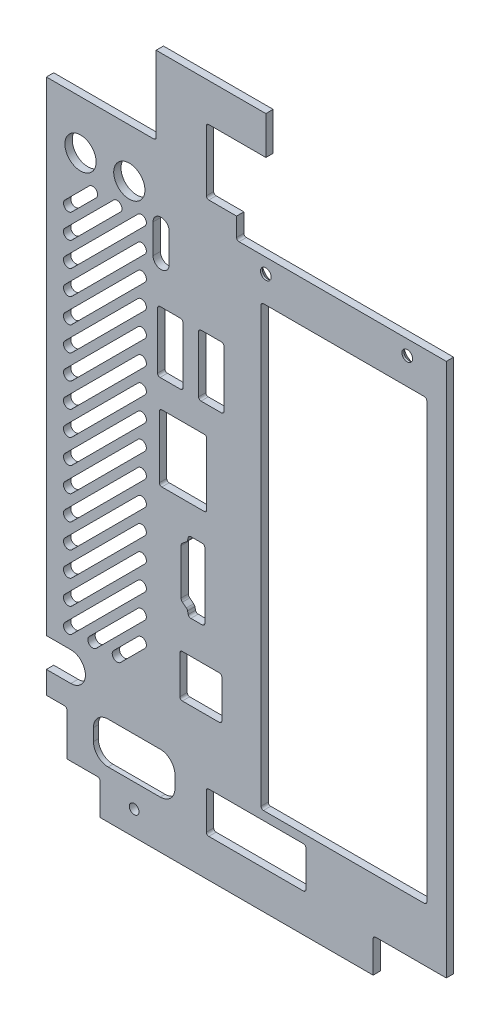
SolidWorks part; units mm, degrees
note: '?' marks a value the reader was unsure of.
ref_plane "前视基准面" through (0, 0, 0) normal (0, 0, 1) x (1, 0, 0)
ref_plane "上视基准面" through (0, 0, 0) normal (0, 1, 0) x (1, 0, 0)
ref_plane "右视基准面" through (0, 0, 0) normal (1, 0, 0) x (0, 0, -1)
sketch "草图1" plane through (0, 0, 0) normal (0, 0, 1) x (1, 0, 0)
  line L2 (-176.1248, 279.7224) -> (-90.1248, 279.7224)
  line L119 (-90.1248, 279.7224) -> (-90.1248, 127.7224)
  line L122 (-90.1248, 127.7224) -> (-176.1248, 127.7224)
  line L125 (-176.1248, 127.7224) -> (-176.1248, 279.7224)
  dimension "D1" = 152
  dimension "D8" = 86
extrude "凸台-拉伸1" add sketch "草图1" along normal blind 1.5
sketch "草图36" plane through (0, 0, 1.5) normal (0, 0, 1) x (1, 0, 0)
  line L0 (-176.1248, 127.7224) -> (-176.1248, 279.7224) construction
  line L1 (-172.1248, 274.7224) -> (-90.1248, 274.7224)
  line L2 (-172.1248, 274.7224) -> (-172.1248, 132.7224)
  line L3 (-172.1248, 132.7224) -> (-90.1248, 132.7224)
  line L4 (-90.1248, 274.7224) -> (-90.1248, 132.7224)
  line L5 (-90.1248, 279.7224) -> (-90.1248, 127.7224) construction
  line L6 (-176.1248, 279.7224) -> (-90.1248, 279.7224) construction
  line L7 (-90.1248, 127.7224) -> (-176.1248, 127.7224) construction
  dimension "D1" = 4
  dimension "D2" = 0
  dimension "D3" = 5
  dimension "D4" = 5
extrude "IO挖空" cut sketch "草图36" against normal blind 10 flip side to cut
sketch "草图38" plane through (0, 0, 0) normal (0, 0, -1) x (-1, 0, 0)
  line L0 (172.1248, 274.7224) -> (172.1248, 132.7224) construction
  line L24 (167.9248, 148.9224) -> (167.9248, 139.7224)
  line L25 (119.1248, 148.7224) -> (139.1248, 148.7224)
  line L26 (119.1248, 148.7224) -> (119.1248, 140.7224)
  line L27 (119.1248, 140.7224) -> (139.1248, 140.7224)
  line L28 (139.1248, 148.7224) -> (139.1248, 140.7224)
  line L35 (172.1248, 132.7224) -> (90.1248, 132.7224) construction
  line L51 (172.1248, 132.7224) -> (161.1248, 132.7224)
  line L52 (172.1248, 274.7224) -> (149.6248, 274.7224)
  line L53 (172.1248, 274.7224) -> (172.1248, 258.7224)
  line L54 (172.1248, 258.7224) -> (149.6248, 258.7224)
  line L55 (149.6248, 274.7224) -> (149.6248, 258.7224)
  line L61 (172.1248, 148.9224) -> (167.9248, 148.9224)
  line L62 (161.1248, 132.7224) -> (161.1248, 139.7224)
  line L69 (172.1248, 132.7224) -> (172.1248, 148.9224)
  line L72 (167.9248, 139.7224) -> (161.1248, 139.7224)
  line L85 (101.1248, 274.7224) -> (90.1248, 274.7224)
  line L86 (90.1248, 274.7224) -> (172.1248, 274.7224) construction
  line L88 (90.1248, 274.7224) -> (90.1248, 257.7224)
  line L89 (90.1248, 274.7224) -> (90.1248, 132.7224) construction
  line L90 (90.1248, 257.7224) -> (101.1248, 257.7224)
  line L94 (101.1248, 257.7224) -> (101.1248, 274.7224)
  line L96 (90.1248, 132.7224) -> (105.1248, 132.7224)
  line L97 (90.1248, 132.7224) -> (90.1248, 139.7224)
  line L98 (90.1248, 139.7224) -> (105.1248, 139.7224)
  line L99 (105.1248, 132.7224) -> (105.1248, 139.7224)
  line L103 (139.3248, 266.9224) -> (115.9248, 266.9224)
  line L104 (139.3248, 266.9224) -> (139.3248, 253.5224)
  line L105 (139.3248, 253.5224) -> (115.9248, 253.5224)
  line L106 (115.9248, 266.9224) -> (115.9248, 253.5224)
  dimension "D2" = 21.2
  dimension "D3" = 8
  dimension "D4" = 20
  dimension "D5" = 16.2
  dimension "D6" = 4.2
  dimension "D7" = 7.8
  dimension "D8" = 32.8
  dimension "D9" = 9.2
  dimension "D10" = 11
  dimension "D11" = 33
extrude "四角挖空" cut sketch "草图38" against normal blind 10
sketch "草图7" plane through (0, 0, 1.5) normal (0, 0, 1) x (1, 0, 0)
  line L0 (-144.7499, 170.6444) -> (-136.1499, 170.6444)
  line L1 (-144.7499, 170.6444) -> (-144.7499, 161.851)
  line L2 (-144.7499, 161.851) -> (-136.1499, 161.851)
  line L3 (-136.1499, 170.6444) -> (-136.1499, 161.851)
  line L4 (-148.9499, 211.4577) -> (-139.2499, 211.4577)
  line L5 (-148.9499, 211.4577) -> (-148.9499, 197.7577)
  line L6 (-148.9499, 197.7577) -> (-139.2499, 197.7577)
  line L7 (-139.2499, 211.4577) -> (-139.2499, 197.7577)
  line L8 (-144.1248, 229.6224) -> (-149.3248, 229.6224)
  line L9 (-144.1248, 229.6224) -> (-144.1248, 217.0224)
  line L10 (-144.1248, 217.0224) -> (-149.3248, 217.0224)
  line L11 (-149.3248, 229.6224) -> (-149.3248, 217.0224)
  line L13 (-140.9248, 229.6224) -> (-135.7248, 229.6224)
  line L14 (-140.9248, 229.6224) -> (-140.9248, 217.0224)
  line L15 (-140.9248, 217.0224) -> (-135.7248, 217.0224)
  line L16 (-135.7248, 229.6224) -> (-135.7248, 217.0224)
  line L18 (-143.4331, 190.516) -> (-144.2193, 189.888)
  line L19 (-143.0354, 191.4831) -> (-143.1729, 190.9231)
  line L20 (-139.6361, 177.952) -> (-139.6361, 191.352)
  line L21 (-143.1729, 178.3808) -> (-143.0354, 177.8208)
  line L22 (-144.2193, 179.416) -> (-143.4331, 178.788)
  line L23 (-142.5012, 191.902) -> (-140.1861, 191.902)
  line L24 (-144.5012, 189.302) -> (-144.5012, 180.002)
  line L25 (-142.5012, 177.402) -> (-140.1861, 177.402)
  line L42 (-90.1248, 257.7224) -> (-90.1248, 139.7224) construction
  line L43 (-172.1248, 258.7224) -> (-149.6248, 258.7224) construction
  line L44 (-172.1248, 258.7224) -> (-172.1248, 148.9224) construction
  line L45 (-150.2548, 243.9224) -> (-146.9548, 243.9224) construction
  line L46 (-150.2548, 243.9224) -> (-150.2548, 237.9224)
  line L47 (-150.2548, 237.9224) -> (-146.9548, 237.9224) construction
  line L48 (-146.9548, 243.9224) -> (-146.9548, 237.9224)
  arc A2 (-144.2193, 189.888) -> (-144.5012, 189.302) centre (-143.7512, 189.302) ccw
  arc A3 (-143.4331, 190.516) -> (-143.1729, 190.9231) centre (-143.9012, 191.102) ccw
  arc A4 (-142.5012, 191.902) -> (-143.0354, 191.4831) centre (-142.5012, 191.352) ccw
  arc A5 (-139.6361, 191.352) -> (-140.1861, 191.902) centre (-140.1861, 191.352) ccw
  arc A6 (-140.1861, 177.402) -> (-139.6361, 177.952) centre (-140.1861, 177.952) ccw
  arc A7 (-143.0354, 177.8208) -> (-142.5012, 177.402) centre (-142.5012, 177.952) ccw
  arc A8 (-143.1729, 178.3808) -> (-143.4331, 178.788) centre (-143.9012, 178.202) ccw
  arc A9 (-144.5012, 180.002) -> (-144.2193, 179.416) centre (-143.7512, 180.002) ccw
  arc A18 (-146.9548, 243.9224) -> (-150.2548, 243.9224) centre (-148.6048, 243.9224) ccw
  arc A19 (-146.9548, 237.9224) -> (-150.2548, 237.9224) centre (-148.6048, 237.9224) cw
  dimension "D6" = 6
  dimension "D14" = 29.1
  dimension "D16" = 29.1
  dimension "D13" = 5.2
  dimension "D2" = 6.7576
  dimension "D3" = 5.8557
  dimension "D4" = 45.6
  dimension "D5" = 5.2
  dimension "D7" = 14.5
  dimension "D8" = 8.7934
  dimension "D9" = 13.7
  dimension "D10" = 12.6
  dimension "D11" = 12.6
  dimension "D12" = 3.3
  dimension "D15" = 3.2
  dimension "D17" = 23.175
extrude "NUC-IO" cut sketch "草图7" against normal blind 2
sketch "草图25" plane through (0, 0, 1.5) normal (0, 0, 1) x (1, 0, 0)
  line L3 (-133.1248, 256.7224) -> (-92.1248, 256.7224)
  line L10 (-128.1248, 150.7224) -> (-94.1248, 150.7224)
  line L27 (-92.1248, 256.7224) -> (-92.1248, 249.2224)
  line L31 (-128.1248, 240.7224) -> (-128.1248, 150.7224)
  line L32 (-161.1248, 132.7224) -> (-105.1248, 132.7224) construction
  line L39 (-92.1248, 249.2224) -> (-133.1248, 249.2224)
  line L40 (-133.1248, 256.7224) -> (-133.1248, 249.2224)
  line L43 (-128.1248, 240.7224) -> (-94.1248, 240.7224)
  line L45 (-94.1248, 240.7224) -> (-94.1248, 150.7224)
  line L47 (-101.1248, 274.7224) -> (-149.6248, 274.7224) construction
  line L48 (-90.1248, 257.7224) -> (-90.1248, 139.7224) construction
  line L49 (-90.1248, 257.7224) -> (-90.1248, 139.7224) construction
  circle A0 centre (-98.1248, 246.2224) radius 1
  circle A1 centre (-127.1248, 246.2224) radius 1
  point P13 (-92.1248, 256.7224)
  dimension "D6" = 41
  dimension "D7" = 5.5
  dimension "D8" = 6
  dimension "D3" = 18
  dimension "D9" = 6
  dimension "D2" = 2
  dimension "D4" = 90
  dimension "D5" = 8.5
  dimension "D10" = 5.5
  dimension "D11" = 18
  dimension "D12" = 4
extrude "PCI-E" cut sketch "草图25" against normal blind 10
sketch "草图31" plane through (0, 0, 1.5) normal (0, 0, 1) x (1, 0, 0)
  line L0 (-172.1248, 258.7224) -> (-172.1248, 148.9224) construction
  line L6 (-162.4748, 148.0224) -> (-162.4748, 145.5224)
  line L19 (-159.4748, 148.0224) -> (-148.7748, 148.0224) construction
  line L20 (-159.4748, 148.0224) -> (-159.4748, 145.5224) construction
  line L21 (-159.4748, 145.5224) -> (-148.7748, 145.5224) construction
  line L22 (-148.7748, 148.0224) -> (-148.7748, 145.5224) construction
  line L23 (-159.4748, 151.0224) -> (-148.7748, 151.0224)
  line L24 (-154.1248, 151.0224) -> (-154.1248, 137.7224) construction
  line L25 (-145.7748, 148.0224) -> (-145.7748, 145.5224)
  line L26 (-159.4748, 142.5224) -> (-148.7748, 142.5224)
  circle A0 centre (-154.1248, 137.7224) radius 1
  arc A5 (-159.4748, 151.0224) -> (-162.4748, 148.0224) centre (-159.4748, 148.0224) ccw
  arc A6 (-162.4748, 145.5224) -> (-159.4748, 142.5224) centre (-159.4748, 145.5224) ccw
  arc A11 (-145.7748, 148.0224) -> (-148.7748, 151.0224) centre (-148.7748, 148.0224) ccw
  arc A12 (-148.7748, 142.5224) -> (-145.7748, 145.5224) centre (-148.7748, 145.5224) ccw
  dimension "D5" = 8.5
  dimension "D1" = 2.5
  dimension "D2" = 10.7
  dimension "D3" = 4.8
  dimension "D4" = 18
extrude "Power" cut sketch "草图31" against normal blind 10
hole_wizard "打孔尺寸(%根据)内六角花形半沉头螺钉的类型1" [suppressed] positions "草图34" profile "草图35" countersink size "M6" standard "GB"
sketch "草图34" plane through (0, 0, 1.5) normal (0, 0, 1) x (1, 0, 0)
  point P0 (-154.1248, 137.7224)
sketch "草图35" plane through (-154.1248, 137.7224, 1.5) normal (1, 0, 0) x (0, -1, 0)
  line L0 (0, 0) -> (0, 1.5)
  line L1 (0, 1.5) -> (1.1, 1.5)
  line L2 (1.1, 1.5) -> (1.1, 1)
  line L3 (1.1, 1) -> (2.1, 0)
  line L5 (2.1, 0) -> (0, 0)
  line L6 (-1.1, 1) -> (-2.1, 0) construction
  line L11 (0, -6.35) -> (0, 107.95) construction
  dimension "通孔孔直径" = 2.2
  dimension "通孔孔深度" = 1.5
  dimension "近端锥形沉头孔直径" = 4.2
  dimension "近端锥形沉头孔角度" = 90
sketch "草图39" plane through (0, 0, 0) normal (0, 0, -1) x (-1, 0, 0)
  line L0 (101.1248, 274.7224) -> (149.6248, 274.7224) construction
  line L1 (114.1248, 271.7224) -> (151.1248, 271.7224) construction
  line L2 (114.1248, 271.7224) -> (114.1248, 135.7224) construction
  line L3 (114.1248, 135.7224) -> (151.1248, 135.7224) construction
  line L4 (151.1248, 271.7224) -> (151.1248, 135.7224) construction
  line L5 (161.1248, 132.7224) -> (105.1248, 132.7224) construction
  line L6 (90.1248, 257.7224) -> (90.1248, 139.7224) construction
  line L7 (172.1248, 258.7224) -> (172.1248, 148.9224) construction
  circle A0 centre (114.1248, 271.7224) radius 1
  circle A1 centre (151.1248, 271.7224) radius 1
  circle A2 centre (114.1248, 135.7224) radius 1
  circle A3 centre (151.1248, 135.7224) radius 1
  dimension "D1" = 3
  dimension "D2" = 3
  dimension "D3" = 24
  dimension "D4" = 21
extrude "IO孔位" [suppressed] cut sketch "草图39" against normal blind 10
sketch "草图46" plane through (0, 0, 1.5) normal (0, 0, 1) x (1, 0, 0)
  line L0 (-177.3005, 156.5224) -> (-167.1248, 156.5224) construction
  line L1 (-177.3005, 159.5224) -> (-167.1248, 159.5224)
  line L2 (-177.3005, 153.5224) -> (-167.1248, 153.5224)
  line L3 (-148.7748, 151.0224) -> (-159.4748, 151.0224) construction
  line L6 (-172.1248, 258.7224) -> (-172.1248, 148.9224) construction
  arc A1 (-177.3005, 159.5224) -> (-177.3005, 153.5224) centre (-177.3005, 156.5224) ccw
  arc A2 (-167.1248, 153.5224) -> (-167.1248, 159.5224) centre (-167.1248, 156.5224) ccw
  circle A3 centre (-167.1248, 156.5224) radius 2.5 construction
  point P2 (-172.2127, 156.5224)
  dimension "D1" = 5
  dimension "D2" = 5.5
extrude "电线口" cut sketch "草图46" against normal blind 2
sketch "草图48" plane through (0, 0, 0) normal (0, 0, -1) x (-1, 0, 0)
  line L5 (133.1248, 259.8891) -> (127.1248, 259.8891)
  line L10 (127.1248, 259.8891) -> (127.1248, 275.7397)
  line L11 (133.1248, 249.2224) -> (90.1248, 249.2224)
  line L12 (133.1248, 249.2224) -> (133.1248, 259.8891)
  line L13 (127.1248, 275.7397) -> (90.1248, 275.7397)
  line L14 (90.1248, 249.2224) -> (90.1248, 275.7397)
  line L15 (172.1248, 258.7224) -> (172.1248, 159.5224) construction
  dimension "D1" = 45
extrude "切除-拉伸1" cut sketch "草图48" against normal blind 10
sketch "草图49" plane through (0, 0, 0) normal (0, 0, -1) x (-1, 0, 0)
  line L0 (94.1248, 240.7224) -> (128.1248, 240.7224) construction
  line L1 (110.3748, 240.7224) -> (114.3748, 240.7224)
  line L2 (110.3748, 240.7224) -> (110.3748, 150.7224)
  line L3 (110.3748, 150.7224) -> (114.3748, 150.7224)
  line L4 (114.3748, 240.7224) -> (114.3748, 150.7224)
  line L5 (128.1248, 150.7224) -> (94.1248, 150.7224) construction
  line L6 (94.1248, 150.7224) -> (94.1248, 240.7224) construction
  dimension "D1" = 4
  dimension "D2" = 16.25
extrude "凸台-拉伸2" [suppressed] add sketch "草图49" against normal blind 1.5
fillet "R1" [suppressed] radius 1
sketch "草图50" plane through (0, 0, 1.5) normal (0, 0, 1) x (1, 0, 0)
  point P0 (-167.1248, 156.5224)
other "线路点1"
ref_plane "基准面1" through (-167.1248, 0, 0) normal (-1, 0, 0) x (0, 0, 1)
sketch3d "3D草图2"
  line L1 (-167.1248, 156.5224, 1.5) -> (-167.1248, 156.5224, 4.5875) construction
  line L3 (-167.1248, 156.5224, 1.8291) -> (-167.1248, 156.5224, -0.8657)
ref_axis "基准轴1" through (-167.1248, 156.5224, 1.8291) along (0, 0, -1)?
sketch "草图54" plane through (0, 0, 1.5) normal (0, 0, 1) x (1, 0, 0)
  line L0 (-127.1248, 274.7224) -> (-149.6248, 274.7224) construction
  line L1 (-172.1248, 258.7224) -> (-172.1248, 159.5224) construction
  circle A0 centre (-155.1248, 248.7224) radius 3.2
  circle A1 centre (-165.1248, 248.7224) radius 3.2
  circle A2 centre (-165.1248, 248.7224) radius 4.5 construction
  circle A3 centre (-155.1248, 248.7224) radius 4.5 construction
  dimension "D1" = 26
  dimension "D2" = 10
  dimension "D3" = 7
extrude "SMA" cut sketch "草图54" against normal blind 1.5
hole_wizard "打孔尺寸(%根据)内六角花形沉头螺钉的类型1" positions "草图55" profile "草图56" countersink size "M6" standard "GB" end condition through all
sketch "草图55" plane through (0, 0, 0) normal (0, 0, -1) x (-1, 0, 0)
  point P0 (98.1248, 246.2224)
  point P3 (127.1248, 246.2224)
sketch "草图56" plane through (-98.1248, 246.2224, 0) normal (1, 0, 0) x (0, 1, 0)
  line L0 (0, 0) -> (0, 1.5)
  line L1 (0, 1.5) -> (1.1, 1.5)
  line L2 (1.1, 1.5) -> (1.1, 1.1)
  line L3 (1.1, 1.1) -> (2.2, 0)
  line L5 (2.2, 0) -> (0, 0)
  line L6 (-1.1, 1.1) -> (-2.2, 0) construction
  line L11 (0, -6.35) -> (0, 107.95) construction
  dimension "通孔孔直径" = 2.2
  dimension "通孔孔深度" = 1.5
  dimension "近端锥形沉头孔直径" = 4.4
  dimension "近端锥形沉头孔角度" = 90
sketch "草图57" plane through (0, 0, 0) normal (0, 0, -1) x (-1, 0, 0)
  line L0 (119.1248, 148.7224) -> (119.1248, 140.7224) construction
  line L1 (118.9248, 148.9224) -> (139.3248, 148.9224)
  line L2 (118.9248, 148.9224) -> (118.9248, 140.5224)
  line L3 (118.9248, 140.5224) -> (139.3248, 140.5224)
  line L4 (139.3248, 148.9224) -> (139.3248, 140.5224)
  line L5 (139.1248, 140.7224) -> (139.1248, 148.7224) construction
  line L6 (119.1248, 140.7224) -> (139.1248, 140.7224) construction
  line L7 (139.1248, 148.7224) -> (119.1248, 148.7224) construction
  dimension "D1" = 0.2
  dimension "D2" = 0.2
  dimension "D3" = 0.2
  dimension "D4" = 0.2
extrude "切除-拉伸4" cut sketch "草图57" against normal blind 10
fillet "圆角1" radius 0.5 7 edges at (-139.3248, 253.5224, 0.75) (-139.3248, 266.9224, 0.75) (-167.9248, 148.9224, 0.75) (-139.3248, 140.5224, 0.75) (-118.9248, 140.5224, 0.75) (-139.3248, 148.9224, 0.75) (-118.9248, 148.9224, 0.75)
sketch "草图59" plane through (0, 0, 0) normal (0, 0, -1) x (-1, 0, 0)
  line L1 (144.1248, 152.7724) -> (164.1248, 152.7724)
  line L2 (144.1248, 152.7724) -> (144.1248, 140.7724)
  line L3 (144.1248, 140.7724) -> (164.1248, 140.7724)
  line L4 (164.1248, 152.7724) -> (164.1248, 140.7724)
  line L5 (159.4748, 142.5224) -> (148.7748, 142.5224) construction
  line L12 (162.4748, 148.0224) -> (162.4748, 145.5224) construction
  dimension "D1" = 20
  dimension "D2" = 12
  dimension "D3" = 1.75
  dimension "D4" = 1.65
extrude "切除-拉伸5" cut sketch "草图59" against normal blind 0.5
fillet "圆角3" radius 0.5 4 edges at (-144.1248, 140.7724, 0.25) (-164.1248, 140.7724, 0.25) (-164.1248, 152.7724, 0.25) (-144.1248, 152.7724, 0.25)
sketch "草图61" plane through (0, 0, 1.5) normal (0, 0, 1) x (1, 0, 0)
  line L0 (-153.1248, 240.9224) -> (-167.1248, 240.9224) construction
  line L1 (-153.1248, 239.4224) -> (-167.1248, 239.4224)
  line L2 (-153.1248, 242.4224) -> (-167.1248, 242.4224)
  line L3 (-172.1248, 258.7224) -> (-172.1248, 159.5224) construction
  line L5 (-153.1248, 236.3724) -> (-167.1248, 236.3724) construction
  line L6 (-153.1248, 234.8724) -> (-167.1248, 234.8724)
  line L7 (-153.1248, 237.8724) -> (-167.1248, 237.8724)
  line L8 (-153.1248, 231.8224) -> (-167.1248, 231.8224) construction
  line L9 (-153.1248, 230.3224) -> (-167.1248, 230.3224)
  line L10 (-153.1248, 233.3224) -> (-167.1248, 233.3224)
  line L11 (-153.1248, 227.2724) -> (-167.1248, 227.2724) construction
  line L12 (-153.1248, 225.7724) -> (-167.1248, 225.7724)
  line L13 (-153.1248, 228.7724) -> (-167.1248, 228.7724)
  line L14 (-153.1248, 222.7224) -> (-167.1248, 222.7224) construction
  line L15 (-153.1248, 221.2224) -> (-167.1248, 221.2224)
  line L16 (-153.1248, 224.2224) -> (-167.1248, 224.2224)
  line L17 (-153.1248, 218.1724) -> (-167.1248, 218.1724) construction
  line L18 (-153.1248, 216.6724) -> (-167.1248, 216.6724)
  line L19 (-153.1248, 219.6724) -> (-167.1248, 219.6724)
  line L20 (-153.1248, 213.6224) -> (-167.1248, 213.6224) construction
  line L21 (-153.1248, 212.1224) -> (-167.1248, 212.1224)
  line L22 (-153.1248, 215.1224) -> (-167.1248, 215.1224)
  line L23 (-153.1248, 209.0724) -> (-167.1248, 209.0724) construction
  line L24 (-153.1248, 207.5724) -> (-167.1248, 207.5724)
  line L25 (-153.1248, 210.5724) -> (-167.1248, 210.5724)
  line L26 (-153.1248, 204.5224) -> (-167.1248, 204.5224) construction
  line L27 (-153.1248, 203.0224) -> (-167.1248, 203.0224)
  line L28 (-153.1248, 206.0224) -> (-167.1248, 206.0224)
  line L29 (-153.1248, 199.9724) -> (-167.1248, 199.9724) construction
  line L30 (-153.1248, 198.4724) -> (-167.1248, 198.4724)
  line L31 (-153.1248, 201.4724) -> (-167.1248, 201.4724)
  line L32 (-153.1248, 195.4224) -> (-167.1248, 195.4224) construction
  line L33 (-153.1248, 193.9224) -> (-167.1248, 193.9224)
  line L34 (-153.1248, 196.9224) -> (-167.1248, 196.9224)
  line L35 (-153.1248, 190.8724) -> (-167.1248, 190.8724) construction
  line L36 (-153.1248, 189.3724) -> (-167.1248, 189.3724)
  line L37 (-153.1248, 192.3724) -> (-167.1248, 192.3724)
  line L38 (-153.1248, 186.3224) -> (-167.1248, 186.3224) construction
  line L39 (-153.1248, 184.8224) -> (-167.1248, 184.8224)
  line L40 (-153.1248, 187.8224) -> (-167.1248, 187.8224)
  line L41 (-153.1248, 181.7724) -> (-167.1248, 181.7724) construction
  line L42 (-153.1248, 180.2724) -> (-167.1248, 180.2724)
  line L43 (-153.1248, 183.2724) -> (-167.1248, 183.2724)
  line L44 (-153.1248, 177.2224) -> (-167.1248, 177.2224) construction
  line L45 (-153.1248, 175.7224) -> (-167.1248, 175.7224)
  line L46 (-153.1248, 178.7224) -> (-167.1248, 178.7224)
  line L47 (-153.1248, 172.6724) -> (-167.1248, 172.6724) construction
  line L48 (-153.1248, 171.1724) -> (-167.1248, 171.1724)
  line L49 (-153.1248, 174.1724) -> (-167.1248, 174.1724)
  line L50 (-153.1248, 168.1224) -> (-167.1248, 168.1224) construction
  line L51 (-153.1248, 166.6224) -> (-167.1248, 166.6224)
  line L52 (-153.1248, 169.6224) -> (-167.1248, 169.6224)
  line L53 (-153.1248, 163.5724) -> (-167.1248, 163.5724) construction
  line L54 (-153.1248, 162.0724) -> (-167.1248, 162.0724)
  line L55 (-153.1248, 165.0724) -> (-167.1248, 165.0724)
  arc A0 (-153.1248, 239.4224) -> (-153.1248, 242.4224) centre (-153.1248, 240.9224) ccw
  arc A1 (-167.1248, 242.4224) -> (-167.1248, 239.4224) centre (-167.1248, 240.9224) ccw
  arc A2 (-153.1248, 234.8724) -> (-153.1248, 237.8724) centre (-153.1248, 236.3724) ccw
  arc A3 (-167.1248, 237.8724) -> (-167.1248, 234.8724) centre (-167.1248, 236.3724) ccw
  arc A4 (-153.1248, 230.3224) -> (-153.1248, 233.3224) centre (-153.1248, 231.8224) ccw
  arc A5 (-167.1248, 233.3224) -> (-167.1248, 230.3224) centre (-167.1248, 231.8224) ccw
  arc A6 (-153.1248, 225.7724) -> (-153.1248, 228.7724) centre (-153.1248, 227.2724) ccw
  arc A7 (-167.1248, 228.7724) -> (-167.1248, 225.7724) centre (-167.1248, 227.2724) ccw
  arc A8 (-153.1248, 221.2224) -> (-153.1248, 224.2224) centre (-153.1248, 222.7224) ccw
  arc A9 (-167.1248, 224.2224) -> (-167.1248, 221.2224) centre (-167.1248, 222.7224) ccw
  arc A10 (-153.1248, 216.6724) -> (-153.1248, 219.6724) centre (-153.1248, 218.1724) ccw
  arc A11 (-167.1248, 219.6724) -> (-167.1248, 216.6724) centre (-167.1248, 218.1724) ccw
  arc A12 (-153.1248, 212.1224) -> (-153.1248, 215.1224) centre (-153.1248, 213.6224) ccw
  arc A13 (-167.1248, 215.1224) -> (-167.1248, 212.1224) centre (-167.1248, 213.6224) ccw
  arc A14 (-153.1248, 207.5724) -> (-153.1248, 210.5724) centre (-153.1248, 209.0724) ccw
  arc A15 (-167.1248, 210.5724) -> (-167.1248, 207.5724) centre (-167.1248, 209.0724) ccw
  arc A16 (-153.1248, 203.0224) -> (-153.1248, 206.0224) centre (-153.1248, 204.5224) ccw
  arc A17 (-167.1248, 206.0224) -> (-167.1248, 203.0224) centre (-167.1248, 204.5224) ccw
  arc A18 (-153.1248, 198.4724) -> (-153.1248, 201.4724) centre (-153.1248, 199.9724) ccw
  arc A19 (-167.1248, 201.4724) -> (-167.1248, 198.4724) centre (-167.1248, 199.9724) ccw
  arc A20 (-153.1248, 193.9224) -> (-153.1248, 196.9224) centre (-153.1248, 195.4224) ccw
  arc A21 (-167.1248, 196.9224) -> (-167.1248, 193.9224) centre (-167.1248, 195.4224) ccw
  arc A22 (-153.1248, 189.3724) -> (-153.1248, 192.3724) centre (-153.1248, 190.8724) ccw
  arc A23 (-167.1248, 192.3724) -> (-167.1248, 189.3724) centre (-167.1248, 190.8724) ccw
  arc A24 (-153.1248, 184.8224) -> (-153.1248, 187.8224) centre (-153.1248, 186.3224) ccw
  arc A25 (-167.1248, 187.8224) -> (-167.1248, 184.8224) centre (-167.1248, 186.3224) ccw
  arc A26 (-153.1248, 180.2724) -> (-153.1248, 183.2724) centre (-153.1248, 181.7724) ccw
  arc A27 (-167.1248, 183.2724) -> (-167.1248, 180.2724) centre (-167.1248, 181.7724) ccw
  arc A28 (-153.1248, 175.7224) -> (-153.1248, 178.7224) centre (-153.1248, 177.2224) ccw
  arc A29 (-167.1248, 178.7224) -> (-167.1248, 175.7224) centre (-167.1248, 177.2224) ccw
  arc A30 (-153.1248, 171.1724) -> (-153.1248, 174.1724) centre (-153.1248, 172.6724) ccw
  arc A31 (-167.1248, 174.1724) -> (-167.1248, 171.1724) centre (-167.1248, 172.6724) ccw
  arc A32 (-153.1248, 166.6224) -> (-153.1248, 169.6224) centre (-153.1248, 168.1224) ccw
  arc A33 (-167.1248, 169.6224) -> (-167.1248, 166.6224) centre (-167.1248, 168.1224) ccw
  arc A34 (-153.1248, 162.0724) -> (-153.1248, 165.0724) centre (-153.1248, 163.5724) ccw
  arc A35 (-167.1248, 165.0724) -> (-167.1248, 162.0724) centre (-167.1248, 163.5724) ccw
  point P2 (-160.1248, 240.9224)
  point P12 (-160.1248, 236.3724)
  point P19 (-160.1248, 231.8224)
  point P26 (-160.1248, 227.2724)
  point P33 (-160.1248, 222.7224)
  point P40 (-160.1248, 218.1724)
  point P47 (-160.1248, 213.6224)
  point P54 (-160.1248, 209.0724)
  point P61 (-160.1248, 204.5224)
  point P68 (-160.1248, 199.9724)
  point P75 (-160.1248, 195.4224)
  point P82 (-160.1248, 190.8724)
  point P89 (-160.1248, 186.3224)
  point P96 (-160.1248, 181.7724)
  point P103 (-160.1248, 177.2224)
  point P110 (-160.1248, 172.6724)
  point P117 (-160.1248, 168.1224)
  point P124 (-160.1248, 163.5724)
  dimension "D2" = 18
  dimension "D1" = 5
extrude "切除-拉伸6" [suppressed] cut sketch "草图61" against normal blind 10
sketch "草图62" plane through (0, 0, 1.5) normal (0, 0, 1) x (1, 0, 0)
  line L0 (-172.1248, 258.7224) -> (-172.1248, 159.5224) construction
  line L1 (-152.6248, 243.9224) -> (-167.6248, 243.9224) construction
  line L2 (-152.6248, 243.9224) -> (-152.6248, 163.0655) construction
  line L3 (-152.6248, 163.0655) -> (-167.6248, 163.0655) construction
  line L4 (-167.6248, 243.9224) -> (-167.6248, 163.0655) construction
  line L5 (-167.6248, 163.0655) -> (-152.6248, 178.0655) construction
  line L6 (-168.332, 163.7726) -> (-153.332, 178.7726)
  line L7 (-166.9177, 162.3584) -> (-151.9177, 177.3584)
  line L8 (-167.6248, 168.0655) -> (-152.6248, 183.0655) construction
  line L9 (-168.332, 168.7726) -> (-153.332, 183.7726)
  line L10 (-166.9177, 167.3584) -> (-151.9177, 182.3584)
  line L11 (-167.6248, 173.0655) -> (-152.6248, 188.0655) construction
  line L12 (-168.332, 173.7726) -> (-153.332, 188.7726)
  line L13 (-166.9177, 172.3584) -> (-151.9177, 187.3584)
  line L14 (-167.6248, 178.0655) -> (-152.6248, 193.0655) construction
  line L15 (-168.332, 178.7726) -> (-153.332, 193.7726)
  line L16 (-166.9177, 177.3584) -> (-151.9177, 192.3584)
  line L17 (-167.6248, 183.0655) -> (-152.6248, 198.0655) construction
  line L18 (-168.332, 183.7726) -> (-153.332, 198.7726)
  line L19 (-166.9177, 182.3584) -> (-151.9177, 197.3584)
  line L20 (-167.6248, 188.0655) -> (-152.6248, 203.0655) construction
  line L21 (-168.332, 188.7726) -> (-153.332, 203.7726)
  line L22 (-166.9177, 187.3584) -> (-151.9177, 202.3584)
  line L23 (-167.6248, 193.0655) -> (-152.6248, 208.0655) construction
  line L24 (-168.332, 193.7726) -> (-153.332, 208.7726)
  line L25 (-166.9177, 192.3584) -> (-151.9177, 207.3584)
  line L26 (-167.6248, 198.0655) -> (-152.6248, 213.0655) construction
  line L27 (-168.332, 198.7726) -> (-153.332, 213.7726)
  line L28 (-166.9177, 197.3584) -> (-151.9177, 212.3584)
  line L29 (-167.6248, 203.0655) -> (-152.6248, 218.0655) construction
  line L30 (-168.332, 203.7726) -> (-153.332, 218.7726)
  line L31 (-166.9177, 202.3584) -> (-151.9177, 217.3584)
  line L32 (-167.6248, 208.0655) -> (-152.6248, 223.0655) construction
  line L33 (-168.332, 208.7726) -> (-153.332, 223.7726)
  line L34 (-166.9177, 207.3584) -> (-151.9177, 222.3584)
  line L35 (-167.6248, 213.0655) -> (-152.6248, 228.0655) construction
  line L36 (-168.332, 213.7726) -> (-153.332, 228.7726)
  line L37 (-166.9177, 212.3584) -> (-151.9177, 227.3584)
  line L38 (-167.6248, 218.0655) -> (-152.6248, 233.0655) construction
  line L39 (-168.332, 218.7726) -> (-153.332, 233.7726)
  line L40 (-166.9177, 217.3584) -> (-151.9177, 232.3584)
  line L41 (-167.6248, 223.0655) -> (-152.6248, 238.0655) construction
  line L42 (-168.332, 223.7726) -> (-153.332, 238.7726)
  line L43 (-166.9177, 222.3584) -> (-151.9177, 237.3584)
  line L44 (-167.6248, 228.0655) -> (-152.6248, 243.0655) construction
  line L45 (-168.332, 228.7726) -> (-153.332, 243.7726)
  line L46 (-166.9177, 227.3584) -> (-151.9177, 242.3584)
  line L47 (-162.6248, 163.0655) -> (-152.6248, 173.0655) construction
  line L50 (-163.332, 163.7726) -> (-153.332, 173.7726)
  line L51 (-161.9177, 162.3584) -> (-151.9177, 172.3584)
  line L52 (-152.6248, 168.0655) -> (-157.6248, 163.0655) construction
  line L53 (-151.9177, 167.3584) -> (-156.9177, 162.3584)
  line L54 (-153.332, 168.7726) -> (-158.332, 163.7726)
  line L55 (-152.6248, 243.0655) -> (-167.6248, 243.0655) construction
  line L57 (-157.6248, 243.0655) -> (-167.6248, 233.0655) construction
  line L58 (-156.9177, 242.3584) -> (-166.9177, 232.3584)
  line L59 (-158.332, 243.7726) -> (-168.332, 233.7726)
  line L60 (-162.6248, 243.0655) -> (-167.6248, 238.0655) construction
  line L61 (-161.9177, 242.3584) -> (-166.9177, 237.3584)
  line L62 (-163.332, 243.7726) -> (-168.332, 238.7726)
  arc A0 (-168.332, 163.7726) -> (-166.9177, 162.3584) centre (-167.6248, 163.0655) ccw
  arc A1 (-151.9177, 177.3584) -> (-153.332, 178.7726) centre (-152.6248, 178.0655) ccw
  arc A2 (-168.332, 168.7726) -> (-166.9177, 167.3584) centre (-167.6248, 168.0655) ccw
  arc A3 (-151.9177, 182.3584) -> (-153.332, 183.7726) centre (-152.6248, 183.0655) ccw
  arc A4 (-168.332, 173.7726) -> (-166.9177, 172.3584) centre (-167.6248, 173.0655) ccw
  arc A5 (-151.9177, 187.3584) -> (-153.332, 188.7726) centre (-152.6248, 188.0655) ccw
  arc A6 (-168.332, 178.7726) -> (-166.9177, 177.3584) centre (-167.6248, 178.0655) ccw
  arc A7 (-151.9177, 192.3584) -> (-153.332, 193.7726) centre (-152.6248, 193.0655) ccw
  arc A8 (-168.332, 183.7726) -> (-166.9177, 182.3584) centre (-167.6248, 183.0655) ccw
  arc A9 (-151.9177, 197.3584) -> (-153.332, 198.7726) centre (-152.6248, 198.0655) ccw
  arc A10 (-168.332, 188.7726) -> (-166.9177, 187.3584) centre (-167.6248, 188.0655) ccw
  arc A11 (-151.9177, 202.3584) -> (-153.332, 203.7726) centre (-152.6248, 203.0655) ccw
  arc A12 (-168.332, 193.7726) -> (-166.9177, 192.3584) centre (-167.6248, 193.0655) ccw
  arc A13 (-151.9177, 207.3584) -> (-153.332, 208.7726) centre (-152.6248, 208.0655) ccw
  arc A14 (-168.332, 198.7726) -> (-166.9177, 197.3584) centre (-167.6248, 198.0655) ccw
  arc A15 (-151.9177, 212.3584) -> (-153.332, 213.7726) centre (-152.6248, 213.0655) ccw
  arc A16 (-168.332, 203.7726) -> (-166.9177, 202.3584) centre (-167.6248, 203.0655) ccw
  arc A17 (-151.9177, 217.3584) -> (-153.332, 218.7726) centre (-152.6248, 218.0655) ccw
  arc A18 (-168.332, 208.7726) -> (-166.9177, 207.3584) centre (-167.6248, 208.0655) ccw
  arc A19 (-151.9177, 222.3584) -> (-153.332, 223.7726) centre (-152.6248, 223.0655) ccw
  arc A20 (-168.332, 213.7726) -> (-166.9177, 212.3584) centre (-167.6248, 213.0655) ccw
  arc A21 (-151.9177, 227.3584) -> (-153.332, 228.7726) centre (-152.6248, 228.0655) ccw
  arc A22 (-168.332, 218.7726) -> (-166.9177, 217.3584) centre (-167.6248, 218.0655) ccw
  arc A23 (-151.9177, 232.3584) -> (-153.332, 233.7726) centre (-152.6248, 233.0655) ccw
  arc A24 (-168.332, 223.7726) -> (-166.9177, 222.3584) centre (-167.6248, 223.0655) ccw
  arc A25 (-151.9177, 237.3584) -> (-153.332, 238.7726) centre (-152.6248, 238.0655) ccw
  arc A26 (-168.332, 228.7726) -> (-166.9177, 227.3584) centre (-167.6248, 228.0655) ccw
  arc A27 (-151.9177, 242.3584) -> (-153.332, 243.7726) centre (-152.6248, 243.0655) ccw
  arc A30 (-163.332, 163.7726) -> (-161.9177, 162.3584) centre (-162.6248, 163.0655) ccw
  arc A31 (-151.9177, 172.3584) -> (-153.332, 173.7726) centre (-152.6248, 173.0655) ccw
  arc A32 (-151.9177, 167.3584) -> (-153.332, 168.7726) centre (-152.6248, 168.0655) ccw
  arc A33 (-158.332, 163.7726) -> (-156.9177, 162.3584) centre (-157.6248, 163.0655) ccw
  arc A34 (-156.9177, 242.3584) -> (-158.332, 243.7726) centre (-157.6248, 243.0655) ccw
  arc A35 (-168.332, 233.7726) -> (-166.9177, 232.3584) centre (-167.6248, 233.0655) ccw
  arc A36 (-161.9177, 242.3584) -> (-163.332, 243.7726) centre (-162.6248, 243.0655) ccw
  arc A37 (-168.332, 238.7726) -> (-166.9177, 237.3584) centre (-167.6248, 238.0655) ccw
  point P6 (-160.1248, 170.5655)
  point P14 (-160.1248, 175.5655)
  point P21 (-160.1248, 180.5655)
  point P28 (-160.1248, 185.5655)
  point P35 (-160.1248, 190.5655)
  point P42 (-160.1248, 195.5655)
  point P49 (-160.1248, 200.5655)
  point P56 (-160.1248, 205.5655)
  point P63 (-160.1248, 210.5655)
  point P70 (-160.1248, 215.5655)
  point P77 (-160.1248, 220.5655)
  point P84 (-160.1248, 225.5655)
  point P91 (-160.1248, 230.5655)
  point P98 (-160.1248, 235.5655)
  point P105 (-157.6248, 168.0655)
  point P112 (-155.1248, 165.5655)
  point P121 (-162.6248, 238.0655)
  point P128 (-165.1248, 240.5655)
  dimension "D2" = 45
  dimension "D4" = 45
  dimension "D6" = 45
  dimension "D8" = 5
  dimension "D11" = 5
  dimension "D1" = 4.5
  dimension "D3" = 14
  dimension "D5" = 5
  dimension "D7" = 5
  dimension "D9" = 45
  dimension "D10" = 15
  dimension "D12" = 45
extrude "切除-拉伸7" cut sketch "草图62" against normal blind 10
fillet "圆角4" radius 0.5 8 edges at (-161.1248, 139.7224, 0.75) (-105.1248, 139.7224, 0.75) (-128.1248, 150.7224, 0.75) (-94.1248, 150.7224, 0.75) (-94.1248, 240.7224, 0.75) (-128.1248, 240.7224, 0.75) (-133.1248, 249.2224, 0.75) (-149.6248, 258.7224, 0.75)
fillet "圆角5" radius 0.5 16 edges at (-144.1248, 217.0224, 0.75) (-140.9248, 217.0224, 0.75) (-149.3248, 217.0224, 0.75) (-144.1248, 229.6224, 0.75) (-149.3248, 229.6224, 0.75) (-140.9248, 229.6224, 0.75) (-135.7248, 229.6224, 0.75) (-135.7248, 217.0224, 0.75) (-148.9499, 197.7577, 0.75) (-139.2499, 197.7577, 0.75) (-139.2499, 211.4577, 0.75) (-148.9499, 211.4577, 0.75) (-144.7499, 161.851, 0.75) (-136.1499, 161.851, 0.75) (-136.1499, 170.6444, 0.75) (-144.7499, 170.6444, 0.75)
